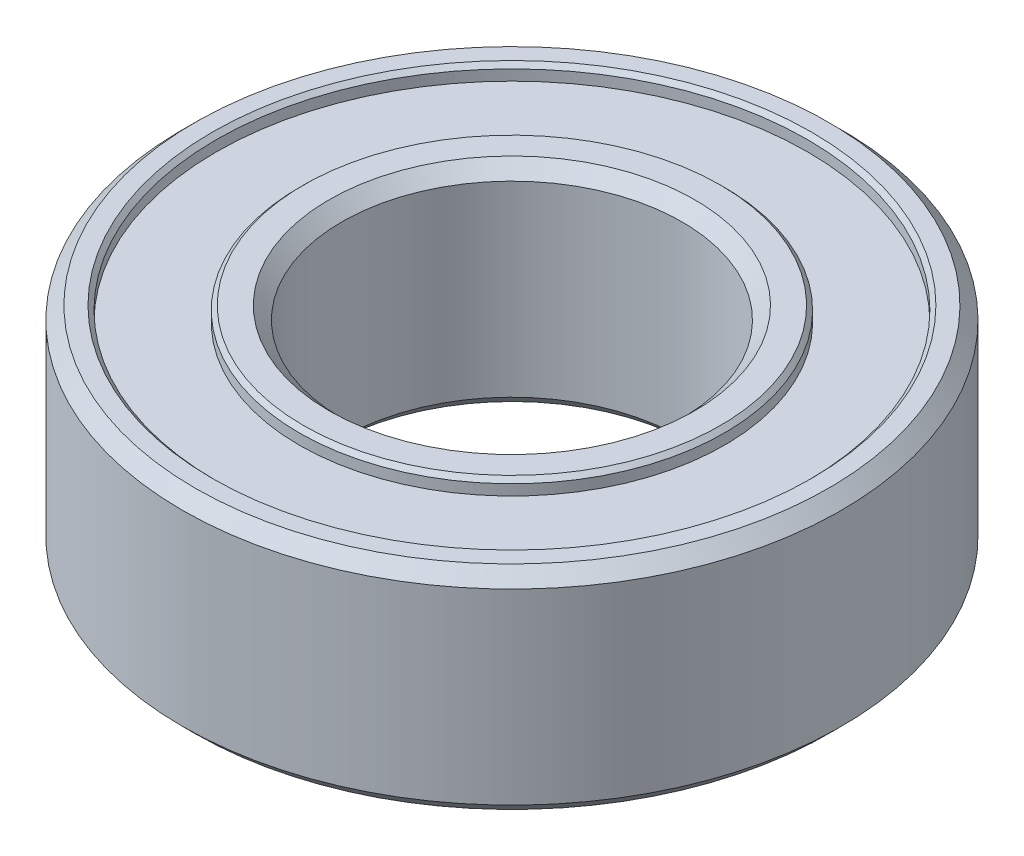
SolidWorks part; units mm, degrees
ref_plane "Front Plane" through (0, 0, 0) normal (0, 0, 1) x (1, 0, 0)
ref_plane "Top Plane" through (0, 0, 0) normal (0, 1, 0) x (1, 0, 0)
ref_plane "Right Plane" through (0, 0, 0) normal (1, 0, 0) x (0, 0, -1)
sketch "Sketch1" plane through (0, 0, 0) normal (0, 1, 0) x (1, 0, 0)
  circle A0 centre (0, 0) radius 15.5
  circle A1 centre (0, 0) radius 13.9
  circle A2 centre (0, 0) radius 10
  circle A3 centre (0, 0) radius 8
  dimension "D1" = 31
  dimension "D2" = 27.8
  dimension "D3" = 20
  dimension "D4" = 16
extrude "Boss-Extrude1" add sketch "Sketch1" along normal blind 10 contours A0 A1 | A2 A3 region at (-15.0616, 0, 0) region at (-9.7172, 0, 0)
ref_plane "Plane1" through (0, 5, 0) normal (0, 1, 0) x (1, 0, 0)
sketch "Sketch2" plane through (0, 5, 0) normal (0, 1, 0) x (1, 0, 0)
  circle A0 centre (0, 0) radius 10
  circle A1 centre (0, 0) radius 13.9
  circle A2 centre (0, 0) radius 10 construction
  circle A3 centre (0, 0) radius 13.9 construction
extrude "Boss-Extrude2" add sketch "Sketch2" along normal offset from surface 0.7 and the other way offset from surface 0.7 up to face at (0, 10, 13.9) other way up to face at (0, 0, 13.9)
chamfer "Chamfer1" distance 0.6 4 edges at (0, 0, 15.5) (0, 0, 8) (0, 10, 8) (0, 10, 15.5)
chamfer "Chamfer2" distance 0.2 angle 45 4 edges at (0, 0, 13.9) (0, 0, 10) (0, 10, 13.9) (0, 10, 10)
